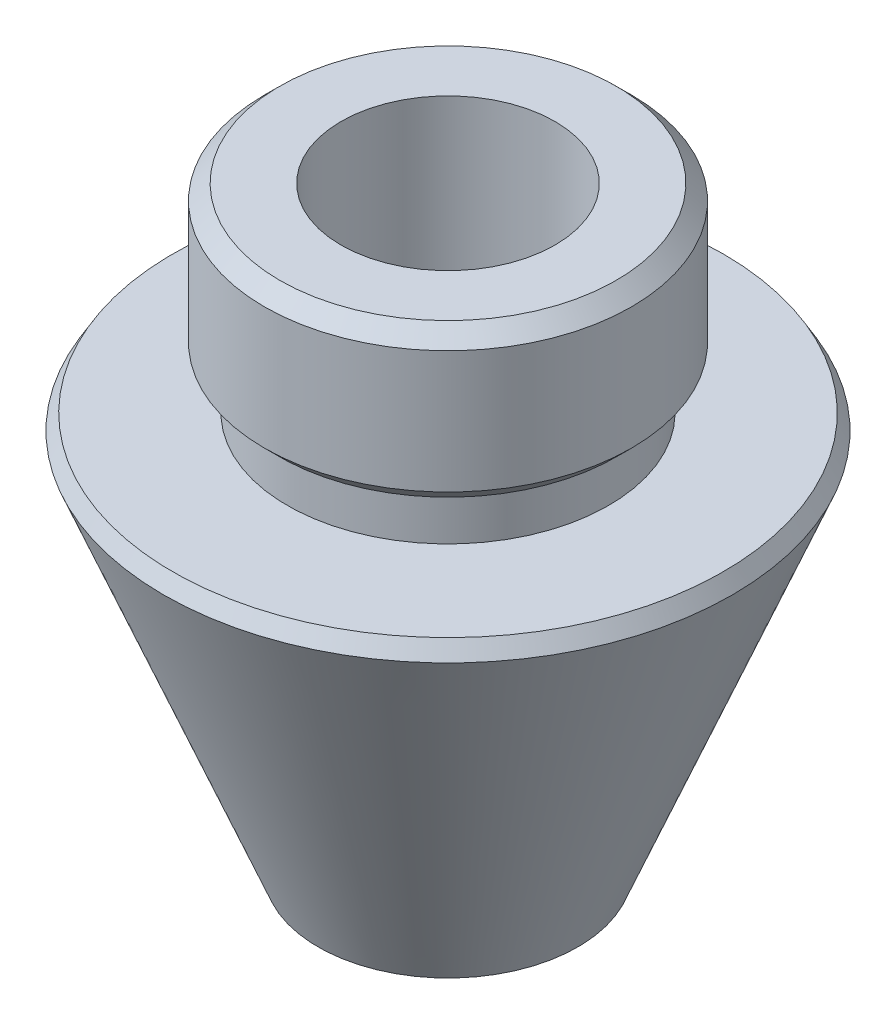
SolidWorks part; units mm, degrees
material "Cobre"
ref_plane "Plano frontal" through (0, 0, 0) normal (0, 0, 1) x (1, 0, 0)
ref_plane "Plano superior" through (0, 0, 0) normal (0, 1, 0) x (1, 0, 0)
ref_plane "Plano direito" through (0, 0, 0) normal (1, 0, 0) x (0, 0, -1)
sketch "Esboço1" plane through (0, 0, 0) normal (1, 0, 0) x (0, 0, -1)
  line L0 (0, 0) -> (0, 40) construction
  line L1 (10.5, 18.7681) -> (19, 18.7681)
  line L2 (19, 18.7681) -> (8.4953, -7.2319)
  line L3 (8.4953, -7.2319) -> (7, -7.2319)
  line L4 (7, 31.7681) -> (7, -7.2319)
  line L5 (-0.5769, 0) -> (1.7552, 0)
  line L6 (10.5, 18.7681) -> (10.5, 21.7681)
  line L7 (10.5, 21.7681) -> (12, 21.7681)
  line L8 (12, 21.7681) -> (12, 31.7681)
  line L9 (12, 31.7681) -> (7, 31.7681)
  line L10 (18, 18.7681) -> (18.5883, 17.7491)
  point P14 (0, 20)
  dimension "D1" = 26
  dimension "D2" = 7
  dimension "D3" = 38
  dimension "D4" = 24
  dimension "D5" = 3
  dimension "D6" = 10
  dimension "D7" = 21
  dimension "D8" = 68
  dimension "D9" = 1
  dimension "D10" = 60
revolve "Revolução1" add sketch "Esboço1" angle 360 about L0 region at (0, 13.3609, -10.6059)
cosmetic thread "Representação de rosca1" parameters "D2"=21.797
chamfer "Chanfro1" distance 1 angle 45 1 edges at (0, 31.7681, -12)
chamfer "Chanfro2" distance 1 angle 45 1 edges at (0, 21.7681, -12)
fillet "Filete1" radius 0.5 1 edges at (0, -7.2319, -7)
